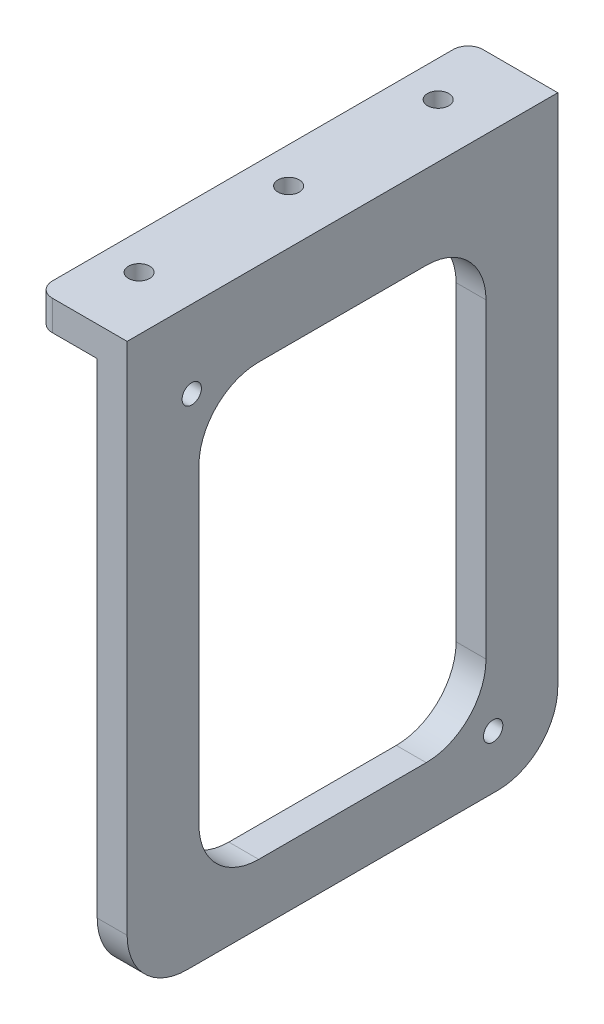
SolidWorks part; units mm, degrees
material "ABS"
ref_plane "Front Plane" through (0, 0, 0) normal (0, 0, 1) x (1, 0, 0)
ref_plane "Top Plane" through (0, 0, 0) normal (0, 1, 0) x (1, 0, 0)
ref_plane "Right Plane" through (0, 0, 0) normal (1, 0, 0) x (0, 0, -1)
sketch "Sketch1" plane through (0, 0, 0) normal (1, 0, 0) x (0, 0, -1)
  line L1 (-22.86, -30.48) -> (22.86, -30.48)
  line L2 (-22.86, -30.48) -> (-22.86, 30.48)
  line L3 (-22.86, 30.48) -> (22.86, 30.48)
  line L4 (22.86, -30.48) -> (22.86, 30.48)
  line L5 (-22.86, -30.48) -> (22.86, 30.48) construction
  line L6 (-22.86, 30.48) -> (22.86, -30.48) construction
  point P0 (0, 0)
  dimension "D1" = 45.72
  dimension "D2" = 60.96
extrude "Boss-Extrude1" add sketch "Sketch1" along normal blind 9.525
sketch "Sketch2" plane through (0, 0, 0) normal (-1, 0, 0) x (0, 0, 1)
  line L0 (22.86, 30.48) -> (22.86, -30.48) construction
  line L1 (-22.86, -30.48) -> (22.86, -30.48)
  line L2 (-22.86, -30.48) -> (-22.86, 27.305)
  line L3 (-22.86, 27.305) -> (22.86, 27.305)
  line L4 (22.86, -30.48) -> (22.86, 27.305)
  line L5 (-22.86, 30.48) -> (22.86, 30.48) construction
  dimension "D1" = 3.175
extrude "Cut-Extrude1" cut sketch "Sketch2" against normal blind 6.35
sketch "Sketch3" plane through (9.525, 0, 0) normal (1, 0, 0) x (0, 0, -1)
  line L2 (-15.24, -24.13) -> (15.24, -24.13)
  line L3 (-15.24, -24.13) -> (-15.24, 21.59)
  line L4 (-15.24, 21.59) -> (15.24, 21.59)
  line L6 (15.24, -24.13) -> (15.24, 21.59)
  line L7 (-15.24, -24.13) -> (15.24, 21.59) construction
  line L8 (-15.24, 21.59) -> (15.24, -24.13) construction
  point P0 (0, -1.27)
  dimension "D1" = 30.48
  dimension "D2" = 45.72
  dimension "D3" = 1.27
extrude "Cut-Extrude2" cut sketch "Sketch3" against normal through all
fillet "Fillet1" radius 6.35 6 edges at (7.9375, -30.48, -22.86) (7.9375, -30.48, 22.86) (7.9375, -24.13, -15.24) (7.9375, -24.13, 15.24) (7.9375, 21.59, -15.24) (7.9375, 21.59, 15.24)
hole_wizard "M2.5x0.45 Tapped Hole1" positions "Sketch5" profile "Sketch4" tap size "M2.5x0.45" standard "Ansi Metric"
sketch "Sketch5" plane through (6.35, 0, 0) normal (-1, 0, 0) x (0, 0, 1)
  line L8 (-16, 22.23) -> (16, 22.23)
  line L9 (-16, 22.23) -> (-16, -24.77)
  line L10 (-16, -24.77) -> (16, -24.77)
  line L11 (16, 22.23) -> (16, -24.77)
  line L12 (-16, 22.23) -> (16, -24.77) construction
  line L13 (-16, -24.77) -> (16, 22.23) construction
  point P0 (16, 22.23)
  point P1 (-16, -24.77)
  point P16 (0, -1.27)
  dimension "D1" = 1.27
  dimension "D3" = 32
  dimension "D4" = 47
sketch "Sketch4" plane through (6.35, 22.23, 16) normal (0, 1, 0) x (0, 0, 1)
  line L0 (0, 0) -> (0, 7.9819)
  line L1 (0, 7.9819) -> (1.025, 7.366)
  line L2 (1.025, 7.366) -> (1.025, 0)
  line L5 (1.025, 0) -> (0, 0)
  line L10 (0, 7.9819) -> (-1.025, 7.366) construction
  line L11 (0, -6.35) -> (0, 107.95) construction
  dimension "Tap Drill Dia." = 2.05
  dimension "Tap Drill Depth" = 7.366
  dimension "Drill Angle" = 118
cosmetic thread "Hole Thread1" parameters "D1"=3.175, "D2"=2.5
cosmetic thread "Hole Thread2" parameters "D1"=3.175, "D2"=2.5
hole_wizard "#4-40 Tapped Hole1" positions "Sketch8" profile "Sketch9" tap size "#4-40" standard "Ansi Inch" end condition up to next
sketch "Sketch8" plane through (0, 30.48, 0) normal (0, 1, 0) x (-1, 0, 0)
  line L0 (0, -22.86) -> (0, 22.86) construction
  point P0 (-3.81, -15.875)
  point P1 (-3.81, 15.875)
  point P4 (-3.81, 0)
  dimension "D1" = 15.875
  dimension "D2" = 15.875
  dimension "D3" = 3.81
sketch "Sketch9" plane through (3.81, 30.48, -15.875) normal (1, 0, 0) x (0, 0, 1)
  line L0 (0, 0) -> (0, 3.175)
  line L1 (0, 3.175) -> (1.1303, 3.175)
  line L2 (1.1303, 3.175) -> (1.1303, 0)
  line L5 (1.1303, 0) -> (0, 0)
  line L11 (0, -6.35) -> (0, 107.95) construction
  dimension "Thru Tap Drill Dia." = 2.2606
  dimension "Thru Tap Drill Depth" = 3.175
cosmetic thread "Hole Thread3" parameters "D2"=2.8448
cosmetic thread "Hole Thread4" parameters "D2"=2.8448
cosmetic thread "Hole Thread5" parameters "D2"=2.8448
fillet "Fillet2" radius 1.5875 2 edges at (0, 28.8925, 22.86) (0, 28.8925, -22.86)
